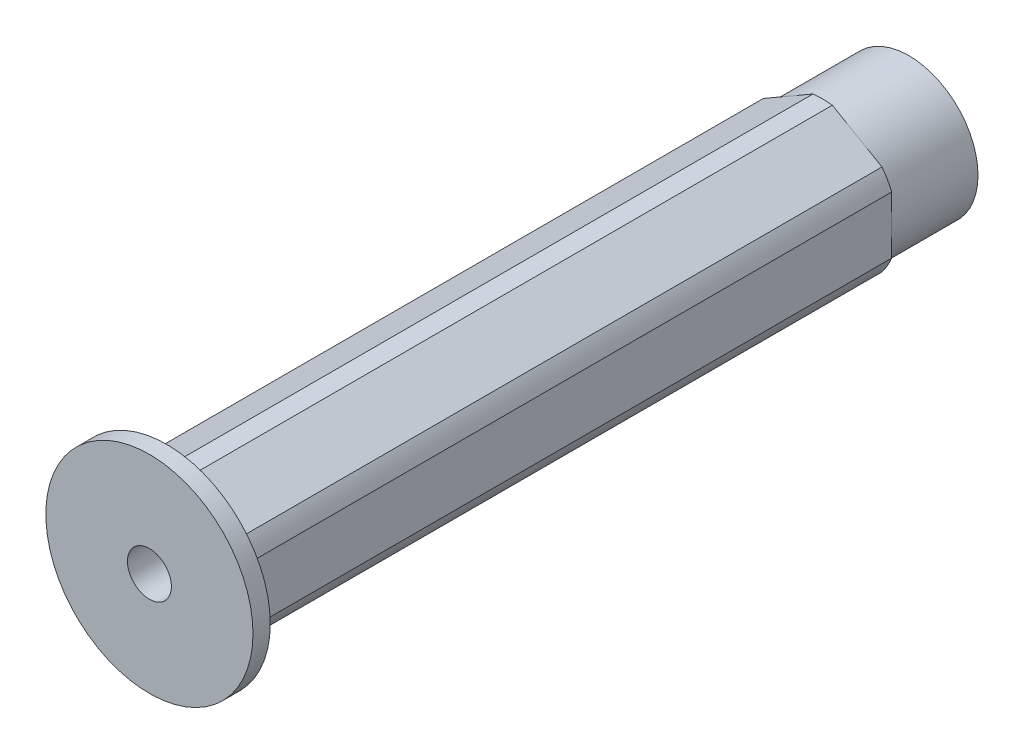
SolidWorks part; units mm, degrees
material "6061-T6 (SS)"
ref_plane "Front Plane" through (0, 0, 0) normal (0, 0, 1) x (1, 0, 0)
ref_plane "Top Plane" through (0, 0, 0) normal (0, 1, 0) x (1, 0, 0)
ref_plane "Right Plane" through (0, 0, 0) normal (1, 0, 0) x (0, 0, -1)
sketch "Sketch1" plane through (0, 0, 0) normal (0, 0, 1) x (1, 0, 0)
  line L0 (0, 7.3323) -> (-0.893, 6.8168) construction
  line L1 (-0.893, 6.8168) -> (-5.457, 4.1818)
  line L2 (-6.35, 2.635) -> (-6.35, -2.635)
  line L3 (-5.457, -4.1818) -> (-0.893, -6.8168)
  line L4 (0.893, -6.8168) -> (5.457, -4.1818)
  line L5 (6.35, -2.635) -> (6.35, 2.635)
  line L6 (5.457, 4.1818) -> (0.893, 6.8168)
  line L7 (0.893, 6.8168) -> (0, 7.3323) construction
  circle A0 centre (0, 0) radius 6.35 construction
  arc A2 (-6.35, -2.635) -> (-5.457, -4.1818) centre (0, 0) ccw
  arc A3 (-5.457, 4.1818) -> (-6.35, 2.635) centre (0, 0) ccw
  arc A4 (0.893, 6.8168) -> (-0.893, 6.8168) centre (0, 0) ccw
  arc A5 (-0.893, -6.8168) -> (0.893, -6.8168) centre (0, 0) ccw
  arc A6 (5.457, -4.1818) -> (6.35, -2.635) centre (0, 0) ccw
  arc A7 (6.35, 2.635) -> (5.457, 4.1818) centre (0, 0) ccw
  dimension "D1" = 12.7
  dimension "D2" = 13.75
extrude "Boss-Extrude1" add sketch "Sketch1" along normal mid plane 68.2625
sketch "Sketch3" plane through (0, 0, 34.1313) normal (0, 0, 1) x (1, 0, 0)
  circle A0 centre (0, 0) radius 2.0193
  dimension "D1" = 4.0386
extrude "Cut-Extrude1" cut sketch "Sketch3" against normal through all
sketch "Sketch8" plane through (0, 0, -34.1313) normal (0, 0, -1) x (-1, 0, 0)
  circle A0 centre (0, 0) radius 6.35
  circle A1 centre (0, 0) radius 6.875
  arc A2 (0.893, 6.8168) -> (-0.893, 6.8168) centre (0, 0) ccw construction
  dimension "D1" = 12.7
extrude "Cut-Extrude3" cut sketch "Sketch8" against normal blind 7.9375
sketch "Sketch9" plane through (0, 0, 34.1313) normal (0, 0, 1) x (1, 0, 0)
  circle A0 centre (0, 0) radius 9.525
  circle A1 centre (0, 0) radius 2.0193
  circle A2 centre (0, 0) radius 2.0193 construction
  dimension "D1" = 19.05
extrude "Boss-Extrude2" add sketch "Sketch9" along normal blind 1.5875
